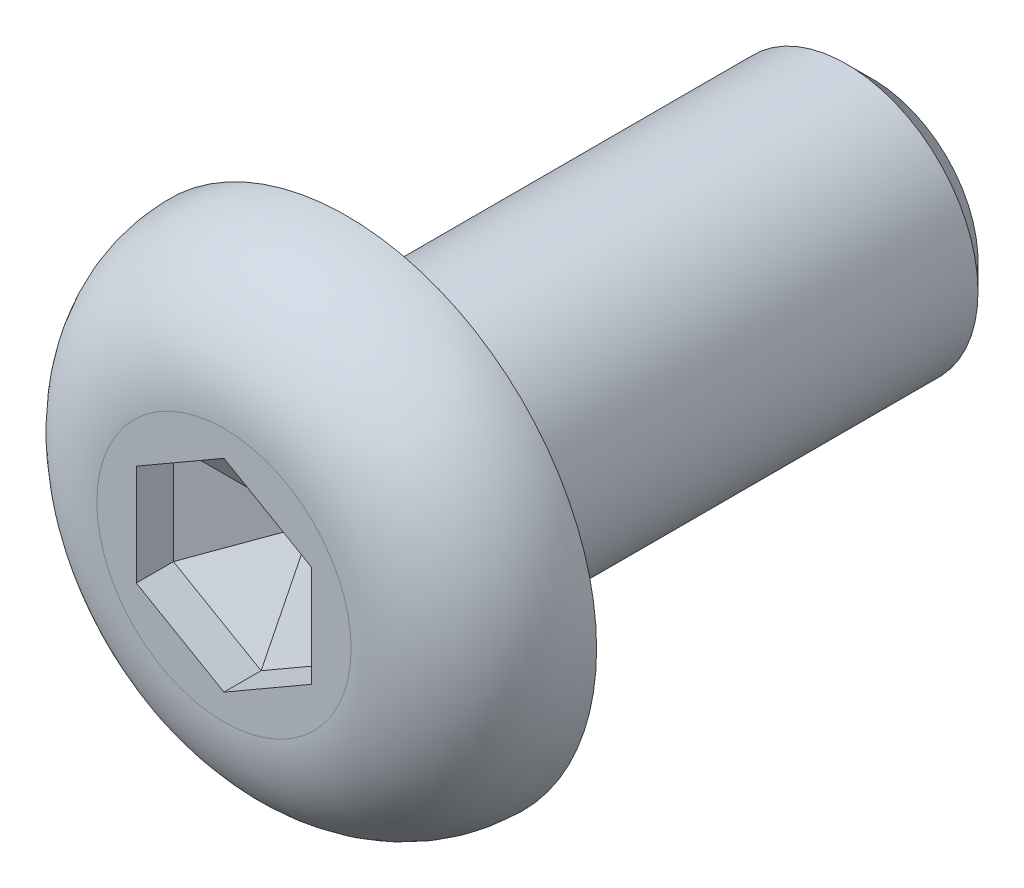
SolidWorks part; units mm, degrees
ref_plane "前视基准面" through (0, 0, 0) normal (0, 0, 1) x (1, 0, 0)
ref_plane "上视基准面" through (0, 0, 0) normal (0, 1, 0) x (1, 0, 0)
ref_plane "右视基准面" through (0, 0, 0) normal (1, 0, 0) x (0, 0, -1)
sketch "草图1" plane through (0, 0, 0) normal (0, 0, 1) x (1, 0, 0)
  circle A0 centre (0, 0) radius 2.85
  dimension "dk" = 5.7
extrude "凸台-拉伸1" add sketch "草图1" along normal blind 1.4
ref_axis "基准轴1" through (0, 0, 1.4) along (0, 0, -1)
fillet "圆角1" radius 1.4 1 edges at (2.85, 0, 1.4)
sketch "草图3" plane through (0, 0, 0) normal (0, 0, -1) x (-1, 0, 0)
  circle A0 centre (0, 0) radius 1.5
  dimension "d" = 3
extrude "凸台-拉伸3" add sketch "草图3" along normal blind 6
cosmetic thread "装饰螺纹线1" parameters "b"=11.9, "D2"=2.459
sketch "草图4" plane through (0, 0, 1.4) normal (0, 0, 1) x (1, 0, 0)
  line L1 (1, 0.5774) -> (0, 1.1547)
  line L2 (0, 1.1547) -> (-1, 0.5774)
  line L3 (-1, 0.5774) -> (-1, -0.5774)
  line L4 (-1, -0.5774) -> (0, -1.1547)
  line L5 (0, -1.1547) -> (1, -0.5774)
  line L6 (1, -0.5774) -> (1, 0.5774)
  circle A0 centre (0, 0) radius 1 construction
  dimension "s" = 2
extrude "切除-拉伸1" cut sketch "草图4" against normal blind 1
chamfer "倒角2" distance 0.3 angle 45 1 edges at (-1.5, 0, -6)
chamfer "倒角3" distance 0.5764 angle 60 6 edges at (-0.5, -0.866, 0.4) (-1, 0, 0.4) (-0.5, 0.866, 0.4) (0.5, 0.866, 0.4) (0.5, -0.866, 0.4) (1, 0, 0.4) first distance on face at (-0.5, -0.866, 0.9) first distance on face at (-1, 0, 0.9) first distance on face at (-0.5, 0.866, 0.9) first distance on face at (0.5, 0.866, 0.9) first distance on face at (0.5, -0.866, 0.9) first distance on face at (1, 0, 0.9)
fillet "圆角2" radius 0.1 1 edges at (1.5, 0, 0)
ref_plane "基准面1" through (0, 0, 0) normal (0, 0, -1) x (-1, 0, 0)
equation "\"D1@倒角3\"=\"s@草图4\" /3.47"
equation "\"D1@倒角2\"= \"d@草图3\" / 10"
equation "\"D1@圆角1\"=\"k@凸台-拉伸1\""
